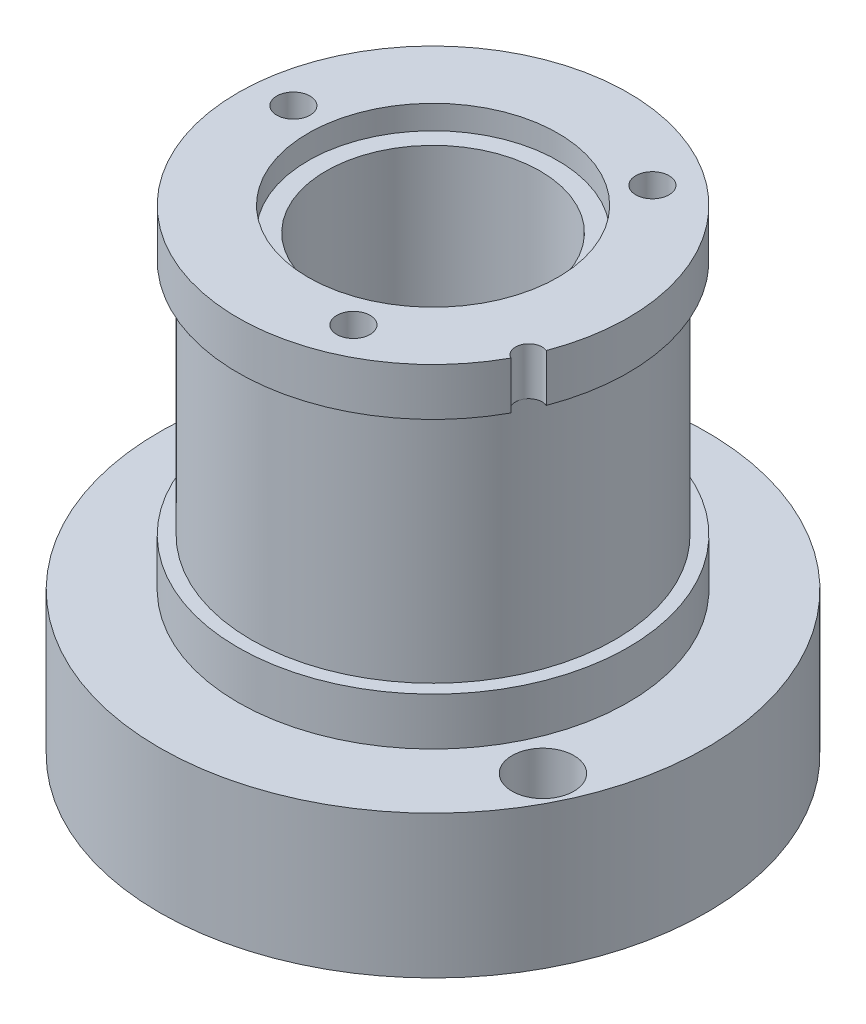
SolidWorks part; units mm, degrees
material "Copper"
ref_plane "Front Plane" through (0, 0, 0) normal (0, 0, 1) x (1, 0, 0)
ref_plane "Top Plane" through (0, 0, 0) normal (0, 1, 0) x (1, 0, 0)
ref_plane "Right Plane" through (0, 0, 0) normal (1, 0, 0) x (0, 0, -1)
sketch "Sketch1" plane through (0, 0, 0) normal (0, 1, 0) x (1, 0, 0)
  circle A0 centre (13.0282, -14.383) radius 14.605
  dimension "D1" = 29.21
extrude "Boss-Extrude2" add sketch "Sketch1" along normal blind 25.4 contours A0
ref_point "Point2"
sketch "Sketch10" plane through (0, 25.4, 0) normal (0, 1, 0) x (1, 0, 0)
  circle A0 centre (13.0282, -14.383) radius 5.715
  dimension "D1" = 11.43
extrude "Cut-Extrude5" cut sketch "Sketch10" against normal through all
sketch "Sketch11" plane through (0, 25.4, 0) normal (0, 1, 0) x (1, 0, 0)
  circle A0 centre (13.0282, -14.383) radius 6.6675
  dimension "D1" = 13.335
extrude "Cut-Extrude6" cut sketch "Sketch11" against normal blind 1.27
sketch "Sketch12" plane through (0, 25.4, 0) normal (0, 1, 0) x (1, 0, 0)
  circle A0 centre (13.0282, -14.383) radius 10.414
  dimension "D1" = 20.828
extrude "Cut-Extrude7" cut sketch "Sketch12" against normal blind 17.78 flip side to cut
sketch "Sketch13" plane through (0, 25.4, 0) normal (0, 1, 0) x (1, 0, 0)
  line L0 (13.0282, -14.383) -> (4.6924, -13.5041)
  dimension "D1" = 8.382
hole_wizard "#50 (0.07) Diameter Hole1" positions "Sketch16" profile "Sketch17" hole size "#50" standard "ANSI Inch"
sketch "Sketch16" plane through (0, 25.4, 0) normal (0, 1, 0) x (1, 0, 0)
  point P0 (4.6924, -13.5041)
sketch "Sketch17" plane through (4.6924, 25.4, 13.5041) normal (1, 0, 0) x (0, 0, 1)
  line L0 (0, 0) -> (0, 3.0742)
  line L1 (0, 3.0742) -> (0.889, 2.54)
  line L2 (0.889, 2.54) -> (0.889, 0)
  line L5 (0.889, 0) -> (0, 0)
  line L10 (0, 3.0742) -> (-0.889, 2.54) construction
  line L11 (0, -6.35) -> (0, 107.95) construction
  dimension "Hole Dia." = 1.778
  dimension "Hole Depth" = 2.54
  dimension "Drill Angle" = 118
pattern_circular "CirPattern1" count 3 over 360 about axis through (13.0282, 7.62, 14.383) along (0, 1, 0) of "#50 (0.07) Diameter Hole1" reverse direction yes
sketch "Sketch18" plane through (0, 0, 0) normal (0, -1, 0) x (-1, 0, 0)
  line L0 (-13.0282, -14.383) -> (-8.1633, -24.3882)
  line L1 (-13.0282, -14.383) -> (-1.6068, -8.8295)
  dimension "D1" = 11.1252
  dimension "D2" = 12.7
hole_wizard "1/16 (0.0625) Diameter Hole2" positions "Sketch23" profile "Sketch24" hole size "1/16" standard "ANSI Inch"
sketch "Sketch23" plane through (0, 0, 0) normal (0, -1, 0) x (-1, 0, 0)
  point P0 (-8.1633, -24.3882)
sketch "Sketch24" plane through (8.1633, 0, 24.3882) normal (1, 0, 0) x (0, 0, -1)
  line L0 (0, 0) -> (0, 4.4774)
  line L1 (0, 4.4774) -> (0.7937, 4.0005)
  line L2 (0.7937, 4.0005) -> (0.7937, 0)
  line L5 (0.7937, 0) -> (0, 0)
  line L10 (0, 4.4774) -> (-0.7938, 4.0005) construction
  line L11 (0, -6.35) -> (0, 107.95) construction
  dimension "Hole Dia." = 1.5875
  dimension "Hole Depth" = 4.0005
  dimension "Drill Angle" = 118
pattern_circular "CirPattern2" count 2 every 180 about axis through (13.0282, 25.4, 14.383) along (0, -1, 0) of "1/16 (0.0625) Diameter Hole2"
sketch "Sketch26" plane through (0, 0, 0) normal (0, -1, 0) x (-1, 0, 0)
  circle A0 centre (-1.6068, -8.8295) radius 1.651
  dimension "D1" = 3.302
extrude "Cut-Extrude8" cut sketch "Sketch26" against normal blind 8.89
pattern_circular "CirPattern3" count 2 every 180 about axis through (13.0282, 25.4, 14.383) along (0, -1, 0) of "Cut-Extrude8" reverse direction yes
sketch "Sketch27" plane through (0, 0, 0) normal (0, -1, 0) x (-1, 0, 0)
  circle A0 centre (-5.8274, -17.1427) radius 0.7938
  dimension "D1" = 1.5875
extrude "Cut-Extrude9" cut sketch "Sketch27" against normal blind 24.13 contours A0
sketch "Sketch30" plane through (0, 0, 0) normal (0, -1, 0) x (-1, 0, 0)
  line L0 (-5.8274, -17.1427) -> (-5.8274, -15.2377)
  line L1 (-5.8274, -17.1427) -> (-5.8274, -19.0477)
  dimension "D1" = 1.905
  dimension "D2" = 1.905
hole_wizard "Tap Drill for #0-80 Tap3" positions "Sketch31" profile "Sketch32" hole size "#0-80" standard "ANSI Inch"
sketch "Sketch31" plane through (0, 0, 0) normal (0, -1, 0) x (-1, 0, 0)
  point P0 (-5.8274, -15.2377)
  point P3 (-5.8274, -19.0477)
sketch "Sketch32" plane through (5.8274, 0, 15.2377) normal (1, 0, 0) x (0, 0, -1)
  line L0 (0, 0) -> (0, 6.8498)
  line L1 (0, 6.8498) -> (0.5956, 6.35)
  line L2 (0.5956, 6.35) -> (0.5956, 0)
  line L5 (0.5956, 0) -> (0, 0)
  line L10 (0, 6.8498) -> (-0.5956, 6.35) construction
  line L11 (0, -6.35) -> (0, 107.95) construction
  dimension "Hole Dia." = 1.1913
  dimension "Hole Depth" = 6.35
  dimension "Drill Angle" = 100
sketch "Sketch33" plane through (0, 7.62, 0) normal (0, 1, 0) x (1, 0, 0)
  circle A0 centre (13.0282, -14.383) radius 10.414
  circle A1 centre (13.0282, -14.383) radius 9.7028
extrude "Cut-Extrude10" cut sketch "Sketch33" along normal blind 15.24
extrude "Boss-Extrude3" add sketch "Sketch33<2>" along normal blind 2.54
sketch "Sketch33<2>" plane through (0, 7.62, 0) normal (0, 1, 0) x (1, 0, 0) same geometry as "Sketch33"
sketch "Sketch35" plane through (0, 25.4, 0) normal (0, 1, 0) x (1, 0, 0)
  circle A0 centre (22.4903, -18.7326) radius 0.7112
  circle A1 centre (13.0282, -14.383) radius 10.414 construction
extrude "Cut-Extrude11" cut sketch "Sketch35" against normal blind 3.556
